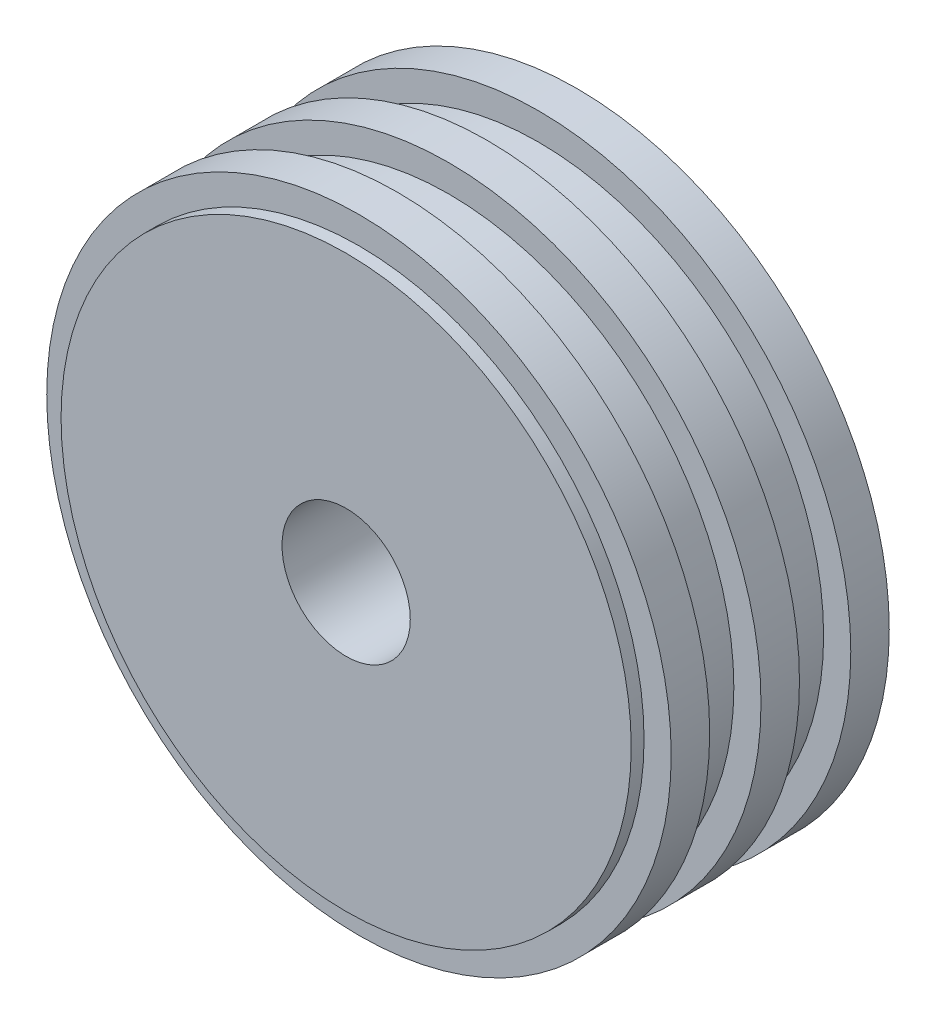
SolidWorks part; units mm, degrees
ref_plane "Front Plane" through (0, 0, 0) normal (0, 0, 1) x (1, 0, 0)
ref_plane "Top Plane" through (0, 0, 0) normal (0, 1, 0) x (1, 0, 0)
ref_plane "Right Plane" through (0, 0, 0) normal (1, 0, 0) x (0, 0, -1)
sketch "Sketch1" plane through (0, 0, 0) normal (0, 0, 1) x (1, 0, 0)
  circle A0 centre (0, 0) radius 66.675
  circle A1 centre (0, 0) radius 15
  dimension "D1" = 133.35
  dimension "D2" = 30
extrude "Boss-Extrude1" add sketch "Sketch1" against normal blind 57
ref_plane "Plane1" through (0, 0, -3) normal (0, 0, 1) x (1, 0, 0)
sketch "Sketch2" plane through (0, 0, -3) normal (0, 0, 1) x (1, 0, 0)
  circle A0 centre (0, 0) radius 66.675 construction
  circle A1 centre (0, 0) radius 66.675
  circle A2 centre (0, 0) radius 73.025
  dimension "D1" = 146.05
extrude "Boss-Extrude2" add sketch "Sketch2" against normal blind 9
ref_axis "Axis1" through (0, 0, -57) along (0, 0, 1)
pattern_linear "LPattern1" count 3 spacing 21 along (0, 0, -1) of "Boss-Extrude2"
